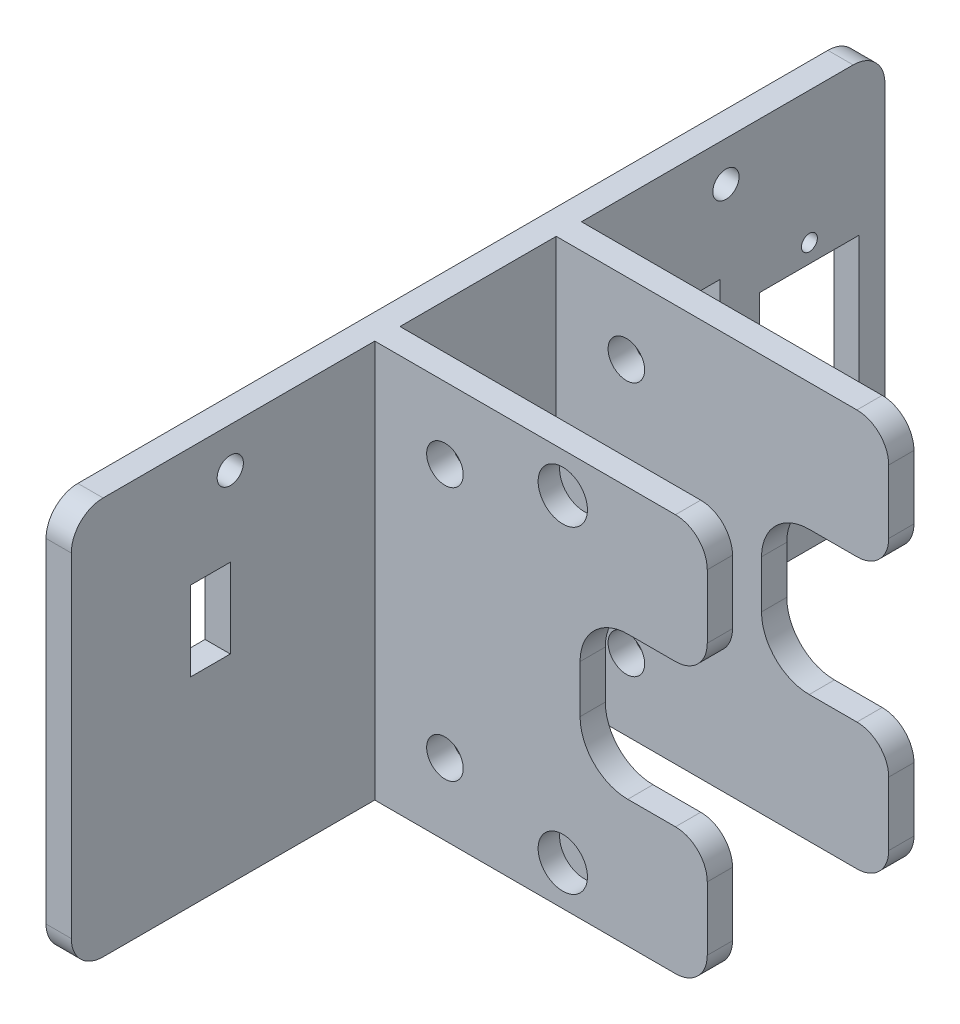
SolidWorks part; units mm, degrees
ref_plane "Front Plane" through (0, 0, 0) normal (0, 0, 1) x (1, 0, 0)
ref_plane "Top Plane" through (0, 0, 0) normal (0, 1, 0) x (1, 0, 0)
ref_plane "Right Plane" through (0, 0, 0) normal (1, 0, 0) x (0, 0, -1)
sketch "Sketch1" plane through (0, 0, 0) normal (0, 1, 0) x (1, 0, 0)
  line L0 (0, 13) -> (0, -13)
  line L5 (0, -13) -> (45, -13)
  line L6 (45, -13) -> (45, -9.825)
  line L17 (45, -9.825) -> (3.175, -9.825)
  line L18 (3.175, -9.825) -> (3.175, 9.825)
  line L19 (0, 0) -> (39.6882, 0) construction
  line L20 (45, 9.825) -> (3.175, 9.825)
  line L21 (45, 13) -> (45, 9.825)
  line L22 (0, 13) -> (45, 13)
  point P9 (3.175, 0)
  dimension "D1" = 26
  dimension "D2" = 3.175
  dimension "D3" = 3.175
  dimension "D4" = 45
extrude "Boss-Extrude1" add sketch "Sketch1" along normal blind 50
sketch "Sketch3" plane through (0, 0, 13) normal (0, 0, 1) x (1, 0, 0)
  line L1 (45, 50) -> (45, 0) construction
  line L2 (0, 50) -> (45, 50) construction
  line L3 (45, 25) -> (0, 25) construction
  line L4 (0, 50) -> (0, 0) construction
  circle A0 centre (26.825, 45) radius 3.1
  circle A2 centre (26.825, 5) radius 3.1
  dimension "D1" = 6.2
  dimension "D2" = 5
  dimension "D3" = 18.175
extrude "Cut-Extrude1" cut sketch "Sketch3" against normal blind 2.7
sketch "Sketch4" plane through (0, 0, -13) normal (0, 0, -1) x (-1, 0, 0)
  line L1 (-45, 50) -> (-45, 0) construction
  line L2 (0, 50) -> (-45, 50) construction
  line L3 (-45, 25) -> (0, 25) construction
  line L4 (0, 50) -> (0, 0) construction
  circle A0 centre (-26.825, 45) radius 3.1
  circle A2 centre (-26.825, 5) radius 3.1
  dimension "D4" = 6.2
  dimension "D1" = 5
  dimension "D2" = 18.175
extrude "Cut-Extrude2" cut sketch "Sketch4" against normal blind 2.7
fillet "Fillet1" radius 4 4 edges at (45, 50, 11.4125) (45, 50, -11.4125) (45, 0, -11.4125) (45, 0, 11.4125)
sketch "Sketch5" plane through (0, 0, 13) normal (0, 0, 1) x (1, 0, 0)
  line L0 (0, 25) -> (45, 25) construction
  line L1 (0, 50) -> (0, 0) construction
  line L2 (45, 46) -> (45, 4) construction
  circle A0 centre (12, 9) radius 2.3
  circle A1 centre (12, 41) radius 2.3
  dimension "D3" = 4.6
  dimension "D1" = 16
  dimension "D2" = 16
  dimension "D4" = 12
extrude "Cut-Extrude3" cut sketch "Sketch5" against normal up to surface (26 mm away) up to face at (23.725, 45, -13)
sketch "Sketch6" plane through (0, 0, 13) normal (0, 0, 1) x (1, 0, 0)
  line L0 (0, 0) -> (41, 0) construction
  line L1 (0, 50) -> (3.175, 50)
  line L2 (0, 50) -> (0, 0)
  line L3 (0, 0) -> (3.175, 0)
  line L4 (3.175, 50) -> (3.175, 0)
  dimension "D1" = 3.175
extrude "Boss-Extrude2" add sketch "Sketch6" along normal blind 38.175
sketch "Sketch7" plane through (0, 0, -13) normal (0, 0, -1) x (-1, 0, 0)
  line L0 (-41, 50) -> (0, 50) construction
  line L1 (0, 0) -> (-3.175, 0)
  line L2 (0, 0) -> (0, 50)
  line L3 (0, 50) -> (-3.175, 50)
  line L4 (-3.175, 0) -> (-3.175, 50)
  dimension "D1" = 3.175
extrude "Boss-Extrude3" add sketch "Sketch7" along normal blind 38.175
fillet "Fillet2" radius 4 4 edges at (1.5875, 0, -51.175) (1.5875, 50, -51.175) (1.5875, 0, 51.175) (1.5875, 50, 51.175)
sketch "Sketch10" plane through (0, 0, 0) normal (-1, 0, 0) x (0, 0, 1)
  line L0 (-51.175, 4) -> (-51.175, 46) construction
  line L3 (-47.175, 0) -> (47.175, 0) construction
  line L5 (-35.425, 31.075) -> (-47.925, 31.075)
  line L6 (-35.425, 31.075) -> (-35.425, 8.325)
  line L7 (-35.425, 8.325) -> (-47.925, 8.325)
  line L8 (-47.925, 31.075) -> (-47.925, 8.325)
  circle A0 centre (-41.675, 6) radius 1
  circle A1 centre (-41.675, 33.4) radius 1
  dimension "D1" = 2
  dimension "D2" = 27.4
  dimension "D3" = 9.5
  dimension "D4" = 6
  dimension "D5" = 12.5
  dimension "D6" = 22.75
  dimension "D7" = 2.325
  dimension "D8" = 6.25
extrude "Cut-Extrude7" cut sketch "Sketch10" against normal up to surface (3.175 mm away) up to face at (3.175, 25, -37.3928)
sketch "Sketch11" plane through (0, 0, 0) normal (-1, 0, 0) x (0, 0, 1)
  line L0 (-51.175, 25) -> (51.175, 25) construction
  line L1 (-51.175, 4) -> (-51.175, 46) construction
  line L2 (51.175, 46) -> (51.175, 4) construction
  line L3 (-47.175, 50) -> (47.175, 50) construction
  circle A2 centre (-31.175, 45) radius 1.65
  circle A3 centre (31.175, 45) radius 1.65
  circle A4 centre (-31.175, 5) radius 1.65
  dimension "D3" = 20
  dimension "D1" = 3.3
  dimension "D2" = 5
  dimension "D4" = 20
extrude "Cut-Extrude8" cut sketch "Sketch11" against normal up to surface (3.175 mm away) up to face at (3.175, 6, -40.675)
sketch "Sketch12" plane through (3.175, 0, 0) normal (1, 0, 0) x (0, 0, -1)
  line L0 (-47.175, 0) -> (-13, 0) construction
  line L1 (-36.175, 25) -> (-31.175, 25)
  line L2 (-36.175, 25) -> (-36.175, 35)
  line L3 (-36.175, 35) -> (-31.175, 35)
  line L4 (-31.175, 25) -> (-31.175, 35)
  line L5 (-51.175, 4) -> (-51.175, 46) construction
  line L6 (47.175, 0) -> (13, 0) construction
  line L7 (25.425, 25) -> (30.425, 25)
  line L8 (25.425, 25) -> (25.425, 35)
  line L9 (25.425, 35) -> (30.425, 35)
  line L10 (30.425, 25) -> (30.425, 35)
  line L11 (35.425, 31.075) -> (35.425, 8.325) construction
  dimension "D1" = 25
  dimension "D2" = 15
  dimension "D3" = 5
  dimension "D4" = 10
  dimension "D5" = 25
  dimension "D6" = 10
  dimension "D7" = 5
  dimension "D8" = 5
extrude "Cut-Extrude9" cut sketch "Sketch12" against normal up to surface (3.175 mm away) up to face at (0, 5, -32.825)
sketch "Sketch13" plane through (0, 0, 13) normal (0, 0, 1) x (1, 0, 0)
  line L0 (45, 46) -> (45, 4) construction
  line L1 (35, 16) -> (45, 16)
  line L2 (29, 22) -> (29, 28)
  line L3 (35, 34) -> (45, 34)
  line L4 (45, 16) -> (45, 34)
  line L5 (45, 25) -> (31.9606, 25) construction
  arc A0 (29, 28) -> (35, 34) centre (35, 28) cw
  arc A1 (35, 16) -> (29, 22) centre (35, 22) cw
  point P14 (29, 16)
  dimension "D3" = 6
  dimension "D1" = 18
  dimension "D2" = 16
extrude "Cut-Extrude10" cut sketch "Sketch13" against normal up to surface (26 mm away) up to face at (29.925, 5, -13)
fillet "Fillet3" radius 4 4 edges at (45, 16, -11.4125) (45, 16, 11.4125) (45, 34, 11.4125) (45, 34, -11.4125)
equation "\"D2@Sketch5\"=\"D1@Sketch5\""
equation "\"D7@Sketch10\"=(\"D2@Sketch10\"-\"D6@Sketch10\")/2"
equation "\"D8@Sketch10\"=\"D5@Sketch10\"/2"
equation "\"D5@Sketch12\"=\"D1@Sketch12\""
equation "\"D6@Sketch12\"=\"D4@Sketch12\""
equation "\"D7@Sketch12\"=\"D3@Sketch12\""
